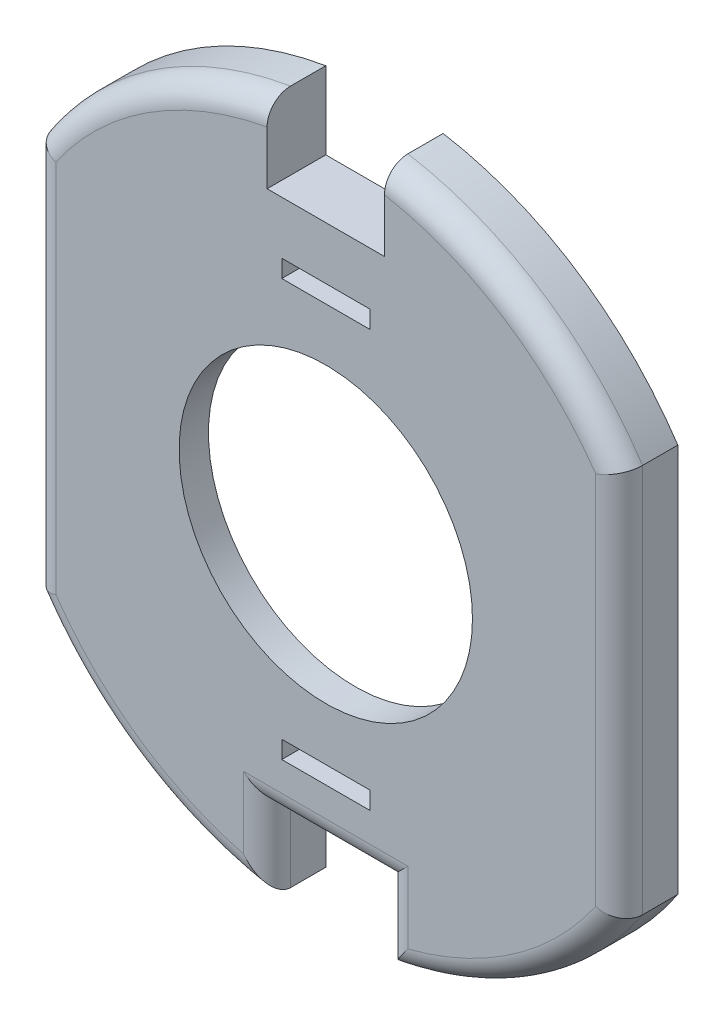
SolidWorks part; units mm, degrees
ref_plane "Front Plane" through (0, 0, 0) normal (0, 0, 1) x (1, 0, 0)
ref_plane "Top Plane" through (0, 0, 0) normal (0, 1, 0) x (1, 0, 0)
ref_plane "Right Plane" through (0, 0, 0) normal (1, 0, 0) x (0, 0, -1)
sketch "Sketch2" plane through (0, 0, 0) normal (0, 0, 1) x (1, 0, 0)
  line L0 (0, 0) -> (0, 50000) construction
  line L1 (0, 0) -> (50000, 0) construction
  line L3 (-5, -3.3166) -> (-5, 3.3166)
  line L4 (5, -3.3166) -> (5, 3.3166)
  line L5 (1, -4.6) -> (1, -5.9161)
  line L6 (1, -4.6) -> (-1, -4.6)
  line L7 (-1, -4.6) -> (-1, -5.9161)
  line L8 (1, 4.6) -> (1, 5.9161)
  line L9 (1, 4.6) -> (-1, 4.6)
  line L10 (-1, 4.6) -> (-1, 5.9161)
  arc A0 (-5, -3.3166) -> (-1, -5.9161) centre (0, 0) ccw
  arc A1 (5, 3.3166) -> (1, 5.9161) centre (0, 0) ccw
  arc A2 (1, -5.9161) -> (5, -3.3166) centre (0, 0) ccw
  arc A3 (-1, 5.9161) -> (-5, 3.3166) centre (0, 0) ccw
  point P15 (0, -4.6)
  dimension "D1" = 2
  dimension "D2" = 1.3161
extrude "Boss-Extrude1" add sketch "Sketch2" along normal blind 1
fillet "Fillet1" radius 0.4 9 edges at (3.2694, 5.031, 1) (5, 0, 1) (3.2694, -5.031, 1) (1, -5.258, 1) (0, -4.6, 1) (-1, -5.258, 1) (-3.2694, -5.031, 1) (-5, 0, 1) (-3.2694, 5.031, 1)
shell "Shell1" thickness 0.5 removed face at (0, 0, 0)
sketch "Sketch3" plane through (0, 0, 1) normal (0, 0, 1) x (1, 0, 0)
  circle A0 centre (0, 0) radius 2.5
extrude "Cut-Extrude1" cut sketch "Sketch3" against normal blind 1
sketch "Sketch4" plane through (0, 0, 1) normal (0, 0, 1) x (1, 0, 0)
  line L0 (0.75, -3.7) -> (-0.75, -3.4) construction
  line L1 (1, 4.6) -> (-1, 4.6) construction
  line L2 (0.75, 3.4) -> (-0.75, 3.4)
  line L3 (0.75, 3.4) -> (0.75, 3.7)
  line L4 (0.75, 3.7) -> (-0.75, 3.7)
  line L5 (-0.75, 3.4) -> (-0.75, 3.7)
  line L6 (0.75, 3.4) -> (-0.75, 3.7) construction
  line L7 (0.75, 3.7) -> (-0.75, 3.4) construction
  line L9 (0.75, -3.4) -> (-0.75, -3.7) construction
  line L10 (-0.75, -3.4) -> (-0.75, -3.7)
  line L11 (0.75, -3.7) -> (-0.75, -3.7)
  line L12 (0.75, -3.4) -> (0.75, -3.7)
  line L13 (0.75, -3.4) -> (-0.75, -3.4)
  dimension "D1" = 0.3
  dimension "D2" = 1.5
  dimension "D3" = 0.9
extrude "Cut-Extrude2" cut sketch "Sketch4" against normal up to next
